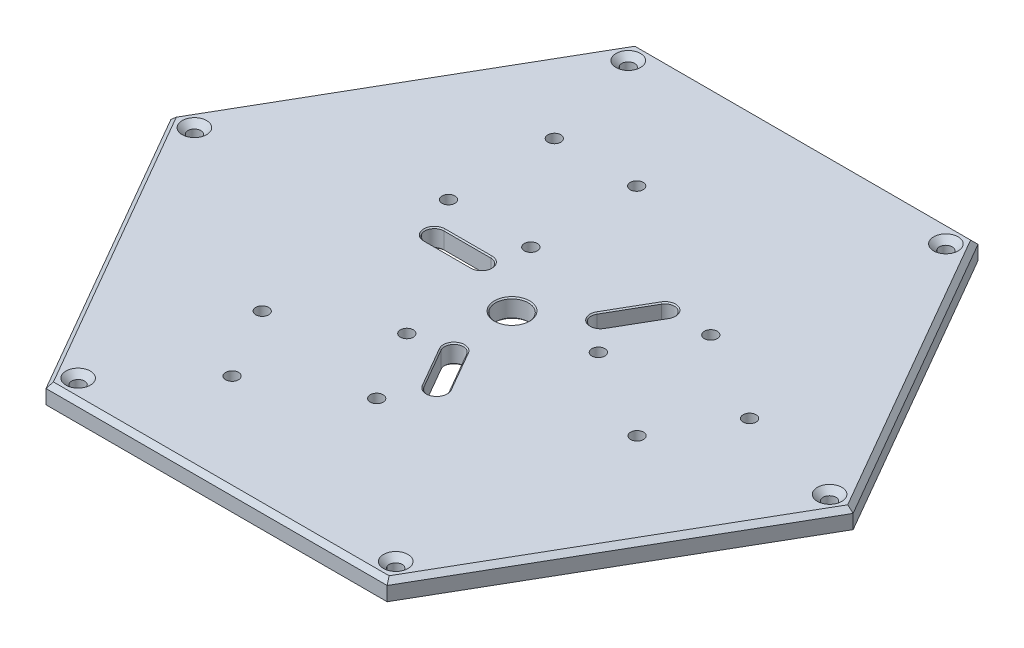
SolidWorks part; units mm, degrees
material "5052-H32"
ref_plane "Front Plane" through (0, 0, 0) normal (0, 0, 1) x (1, 0, 0)
ref_plane "Top Plane" through (0, 0, 0) normal (0, 1, 0) x (1, 0, 0)
ref_plane "Right Plane" through (0, 0, 0) normal (1, 0, 0) x (0, 0, -1)
sketch "Sketch1" plane through (0, 0, 0) normal (0, 1, 0) x (1, 0, 0)
  line L1 (72.5, 125.5737) -> (-72.5, 125.5737)
  line L2 (-72.5, 125.5737) -> (-145, 0)
  line L3 (-145, 0) -> (-72.5, -125.5737)
  line L4 (-72.5, -125.5737) -> (72.5, -125.5737)
  line L5 (72.5, -125.5737) -> (145, 0)
  line L6 (145, 0) -> (72.5, 125.5737)
  circle A0 centre (0, 0) radius 125.5737 construction
  dimension "D1" = 145
extrude "Boss-Extrude1" add sketch "Sketch1" along normal blind 8
sketch "Sketch2" plane through (0, 0, 0) normal (0, 1, 0) x (1, 0, 0)
  line L0 (0, 0) -> (108.75, 62.7868) construction
  line L1 (145, 0) -> (72.5, 125.5737) construction
  line L2 (70.5513, 22.1984) -> (53.0513, -8.1125) construction
  line L3 (66.5368, -29.7548) -> (27.5657, -7.2548) construction
  line L6 (33.5657, 3.1375) -> (72.5368, -19.3625) construction
  line L7 (72.5368, -19.3625) -> (90.0368, 10.9484) construction
  line L8 (90.0368, 10.9484) -> (51.0657, 33.4484) construction
  line L9 (51.0657, 33.4484) -> (33.5657, 3.1375) construction
  line L10 (-14.0657, -30.6375) -> (-53.0368, -53.1375) construction
  line L11 (3.4343, -60.9484) -> (-14.0657, -30.6375) construction
  line L12 (-35.5368, -83.4484) -> (3.4343, -60.9484) construction
  line L13 (-53.0368, -53.1375) -> (-35.5368, -83.4484) construction
  line L14 (-19.5, 27.5) -> (-19.5, 72.5) construction
  line L15 (-54.5, 27.5) -> (-19.5, 27.5) construction
  line L16 (-54.5, 72.5) -> (-54.5, 27.5) construction
  line L17 (-19.5, 72.5) -> (-54.5, 72.5) construction
  line L19 (53.0513, -8.1125) -> (43.3013, -25) construction
  line L21 (108.75, -62.7868) -> (0, 0) construction
  line L22 (72.5, -125.5737) -> (145, 0) construction
  point P9 (47.0513, -18.5048)
  point P18 (33.5657, 3.1375)
  point P19 (51.0657, 33.4484)
  point P20 (90.0368, 10.9484)
  point P21 (72.5368, -19.3625)
  point P31 (0, 0)
  dimension "D1" = 45
  dimension "D2" = 35
  dimension "D4" = 7.5
  dimension "D5" = 12
  dimension "D6" = 50
  dimension "D3" = 3
sketch "Sketch5" plane through (0, 8, 0) normal (0, 1, 0) x (1, 0, 0)
  circle A0 centre (0, 0) radius 7
  dimension "D1" = 14
extrude "Cut-Extrude1" cut sketch "Sketch5" against normal through all
hole_wizard "CSK for M5 Flat Head Machine Screw1" positions "Sketch7" profile "Sketch6" countersink size "M5" standard "ANSI Metric" end condition through all
sketch "Sketch7" plane through (0, 0, 0) normal (0, -1, 0) x (-1, 0, 0)
  point P0 (54.5, 27.5)
  point P3 (19.5, 27.5)
  point P6 (19.5, 72.5)
  point P9 (54.5, 72.5)
  point P12 (-33.5657, 3.1375)
  point P15 (-72.5368, -19.3625)
  point P18 (-90.0368, 10.9484)
  point P21 (-51.0657, 33.4484)
  point P24 (14.0657, -30.6375)
  point P27 (-3.4343, -60.9484)
  point P30 (35.5368, -83.4484)
  point P33 (53.0368, -53.1375)
sketch "Sketch6" plane through (-54.5, 0, -27.5) normal (1, 0, 0) x (0, 0, -1)
  line L0 (0, 0) -> (0, 8)
  line L1 (0, 8) -> (2.75, 8)
  line L2 (2.75, 8) -> (2.75, 2.45)
  line L3 (2.75, 2.45) -> (5.2, 0)
  line L5 (5.2, 0) -> (0, 0)
  line L6 (-2.75, 2.45) -> (-5.2, 0) construction
  line L11 (0, -6.35) -> (0, 107.95) construction
  dimension "Thru Hole Dia." = 5.5
  dimension "Thru Hole Depth" = 8
  dimension "Near C'Sink Dia." = 10.4
  dimension "Near C'Sink Angle" = 90
sketch "Sketch9" plane through (0, 0, 0) normal (0, -1, 0) x (1, 0, 0)
  line L0 (32.2093, -32.7881) -> (22.2093, -15.4676) construction
  line L1 (28.7452, -34.7881) -> (18.7452, -17.4676)
  line L2 (35.6734, -30.7881) -> (25.6734, -13.4676)
  line L3 (19.7093, -11.1375) -> (37.2093, -41.4484) construction
  line L4 (90.0368, -10.9484) -> (51.0657, -33.4484) construction
  line L5 (33.5657, -3.1375) -> (72.5368, 19.3625) construction
  line L6 (51.0657, -33.4484) -> (33.5657, -3.1375) construction
  line L7 (-44.5, -11.5) -> (-24.5, -11.5) construction
  line L8 (-44.5, -7.5) -> (-24.5, -7.5)
  line L9 (-44.5, -15.5) -> (-24.5, -15.5)
  line L10 (12.2907, 44.2881) -> (2.2907, 26.9676) construction
  line L11 (15.7548, 42.2881) -> (5.7548, 24.9676)
  line L12 (8.8266, 46.2881) -> (-1.1734, 28.9676)
  arc A0 (28.7452, -34.7881) -> (35.6734, -30.7881) centre (32.2093, -32.7881) ccw
  arc A1 (25.6734, -13.4676) -> (18.7452, -17.4676) centre (22.2093, -15.4676) ccw
  arc A2 (-44.5, -7.5) -> (-44.5, -15.5) centre (-44.5, -11.5) ccw
  arc A3 (-24.5, -15.5) -> (-24.5, -7.5) centre (-24.5, -11.5) ccw
  arc A4 (15.7548, 42.2881) -> (8.8266, 46.2881) centre (12.2907, 44.2881) ccw
  arc A5 (-1.1734, 28.9676) -> (5.7548, 24.9676) centre (2.2907, 26.9676) ccw
  point P2 (27.2093, -24.1279)
  point P19 (-34.5, -11.5)
  point P26 (7.2907, 35.6279)
  point P31 (0, 0)
  dimension "D1" = 16
  dimension "D2" = 8
  dimension "D3" = 20
  dimension "D5" = 20
  dimension "D4" = 3
extrude "Cut-Extrude3" cut sketch "Sketch9" against normal through all
sketch "Sketch10" plane through (0, 8, 0) normal (0, 1, 0) x (1, 0, 0)
  line L0 (145, 0) -> (0, 0) construction
  point P4 (135, 0)
  point P7 (67.5, -116.9134)
  point P8 (-67.5, -116.9134)
  point P9 (-135, 0)
  point P10 (-67.5, 116.9134)
  point P11 (67.5, 116.9134)
  point P12 (0, 0)
  dimension "D2" = 10
  dimension "D1" = 6
hole_wizard "CSK for M5 Flat Head Machine Screw2" positions "Sketch14" profile "Sketch13" countersink size "M5" standard "ANSI Metric"
sketch "Sketch14" plane through (0, 8, 0) normal (0, 1, 0) x (1, 0, 0)
  point P0 (-135, 0)
  point P3 (-67.5, -116.9134)
  point P6 (67.5, -116.9134)
  point P9 (135, 0)
  point P12 (67.5, 116.9134)
  point P15 (-67.5, 116.9134)
sketch "Sketch13" plane through (-135, 8, 0) normal (1, 0, 0) x (0, 0, 1)
  line L0 (0, 0) -> (0, 11.6524)
  line L1 (0, 11.6524) -> (2.75, 10)
  line L2 (2.75, 10) -> (2.75, 2.45)
  line L3 (2.75, 2.45) -> (5.2, 0)
  line L5 (5.2, 0) -> (0, 0)
  line L6 (-2.75, 2.45) -> (-5.2, 0) construction
  line L10 (0, 11.6524) -> (-2.75, 10) construction
  line L11 (0, -6.35) -> (0, 107.95) construction
  dimension "Hole Dia." = 5.5
  dimension "Hole Depth" = 10
  dimension "Near C'Sink Dia." = 10.4
  dimension "Near C'Sink Angle" = 90
  dimension "Drill Angle" = 118
chamfer "Chamfer1" distance 0.5 angle 45 24 edges at (-34.5, 0, -15.5) (-20.5, 0, -11.5) (-48.5, 0, -11.5) (-34.5, 0, -7.5) (23.7452, 0, -26.1279) (34.2093, 0, -36.2522) (20.2093, 0, -12.0035) (30.6734, 0, -22.1279) (3.8266, 0, 37.6279) (0.2907, 0, 23.5035) (14.2907, 0, 47.7522) (10.7548, 0, 33.6279) (-34.5, 8, -15.5) (-20.5, 8, -11.5) (-48.5, 8, -11.5) (-34.5, 8, -7.5) (23.7452, 8, -26.1279) (34.2093, 8, -36.2522) (20.2093, 8, -12.0035) (30.6734, 8, -22.1279) (3.8266, 8, 37.6279) (0.2907, 8, 23.5035) (14.2907, 8, 47.7522) (10.7548, 8, 33.6279)
sketch "Sketch8" plane through (0, 0, 0) normal (0, -1, 0) x (1, 0, 0)
  line L0 (104.25, 70.5811) -> (113.25, 54.9926)
  line L1 (104.25, 70.5811) -> (66.9471, 49.0442)
  line L2 (113.25, 54.9926) -> (75.9471, 33.4558)
  line L3 (66.9471, 49.0442) -> (75.9471, 33.4558)
  line L4 (72.5, 125.5737) -> (145, 0) construction
  line L5 (108.75, 62.7868) -> (0, 0) construction
  line L7 (9, -125.5737) -> (-9, -125.5737)
  line L8 (9, -125.5737) -> (9, -82.5)
  line L9 (-9, -125.5737) -> (-9, -82.5)
  line L10 (9, -82.5) -> (-9, -82.5)
  line L11 (-113.25, 54.9926) -> (-104.25, 70.5811)
  line L12 (-113.25, 54.9926) -> (-75.9471, 33.4558)
  line L13 (-104.25, 70.5811) -> (-66.9471, 49.0442)
  line L14 (-75.9471, 33.4558) -> (-66.9471, 49.0442)
  circle A0 centre (0, 0) radius 7 construction
  point P6 (108.75, 62.7868)
  point P22 (0, 0)
  dimension "D1" = 18
  dimension "D2" = 10
  dimension "D3" = 3
extrude "Cut-Extrude2" [suppressed] cut sketch "Sketch8" against normal through all
chamfer "Chamfer3" distance 0.5 angle 45 2 edges at (0, 8, 7) (0, 0, 7)
chamfer "Chamfer4" distance 2 angle 45 6 edges at (0, 8, 125.5737) (108.75, 8, 62.7868) (108.75, 8, -62.7868) (0, 8, -125.5737) (-108.75, 8, -62.7868) (-108.75, 8, 62.7868)
